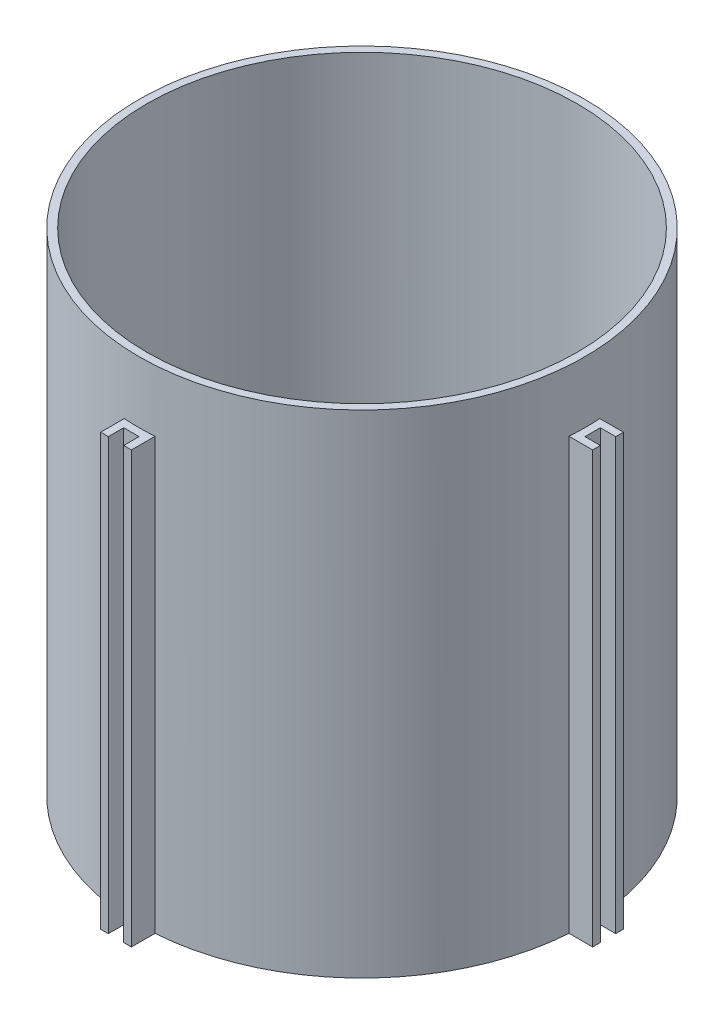
SolidWorks part; units mm, degrees
ref_plane "Front Plane" through (0, 0, 0) normal (0, 0, 1) x (1, 0, 0)
ref_plane "Top Plane" through (0, 0, 0) normal (0, 1, 0) x (1, 0, 0)
ref_plane "Right Plane" through (0, 0, 0) normal (1, 0, 0) x (0, 0, -1)
sketch "Sketch1" plane through (0, 0, 0) normal (0, 1, 0) x (1, 0, 0)
  circle A0 centre (0, 0) radius 92.075
  circle A1 centre (0, 0) radius 88.9
  dimension "D1" = 184.15
  dimension "D2" = 177.8
extrude "Base Shell" add sketch "Sketch1" along normal blind 203.2
sketch "Sketch2" plane through (0, 0, 0) normal (0, -1, 0) x (1, 0, 0)
  circle A1 centre (0, 0) radius 69.85 construction
  circle A2 centre (0, 0) radius 88.9 construction
  circle A3 centre (0, 0) radius 88.9
  arc A4 (-78.8035, -9.5078) -> (-9.5078, -78.8035) centre (0, 0) ccw
  circle A5 centre (0, 79.375) radius 3.175
  circle A6 centre (79.375, 0) radius 3.175
  circle A7 centre (0, -79.375) radius 3.175
  circle A8 centre (-79.375, 0) radius 3.175
  arc A9 (-9.5078, 78.8035) -> (9.5078, 78.8035) centre (0, 79.375) ccw
  arc A10 (78.8035, 9.5078) -> (78.8035, -9.5078) centre (79.375, 0) ccw
  arc A11 (9.5078, -78.8035) -> (-9.5078, -78.8035) centre (0, -79.375) ccw
  arc A12 (-78.8035, -9.5078) -> (-78.8035, 9.5078) centre (-79.375, 0) ccw
  arc A13 (-9.5078, 78.8035) -> (-78.8035, 9.5078) centre (0, 0) ccw
  arc A14 (78.8035, 9.5078) -> (9.5078, 78.8035) centre (0, 0) ccw
  arc A15 (9.5078, -78.8035) -> (78.8035, -9.5078) centre (0, 0) ccw
  point P18 (0, 0)
  point P26 (0, 0)
  dimension "D1" = 139.7
extrude "Bolt Insert" add sketch "Sketch2" against normal blind 6.35
sketch "Sketch3" plane through (0, 0, 0) normal (0, 1, 0) x (1, 0, 0)
  line L0 (-6.35, 0) -> (6.35, 0)
  line L7 (-6.35, 101.6) -> (-3.175, 101.6)
  line L9 (0, 101.6) -> (0, 92.075) construction
  line L10 (-6.35, 101.6) -> (-5.7435, 91.8957) construction
  line L11 (-6.35, 91.8558) -> (-6.35, 101.6)
  line L12 (5.7435, 91.8957) -> (6.35, 101.6) construction
  line L14 (6.35, 91.8558) -> (6.35, 101.6)
  line L15 (-3.175, 101.6) -> (-3.175, 95.25)
  line L16 (-3.175, 95.25) -> (3.175, 95.25)
  line L17 (3.175, 101.6) -> (3.175, 95.25)
  line L18 (0, 101.6) -> (3.175, 95.25) construction
  line L19 (-3.175, 95.25) -> (0, 101.6) construction
  line L20 (3.175, 101.6) -> (6.35, 101.6)
  circle A2 centre (0, 0) radius 92.075 construction
  arc A3 (6.35, 91.8558) -> (-6.35, 91.8558) centre (0, 0) ccw
  point P1 (0, 101.6)
  dimension "D1" = 12.7
  dimension "D2" = 101.6
  dimension "D3" = 6.35
  dimension "D4" = 3.175
  dimension "D5" = 3.175
extrude "Fin Bracket" add sketch "Sketch3" along normal blind 177.8 contours A3 L14 L20 L17 L16 L15 L7 L11 region at (-4.7625, 0, -101.4399)
pattern_circular "CirPattern1" count 4 over 360 about axis through (0, 203.2, 0) along (0, -1, 0) of "Fin Bracket"
